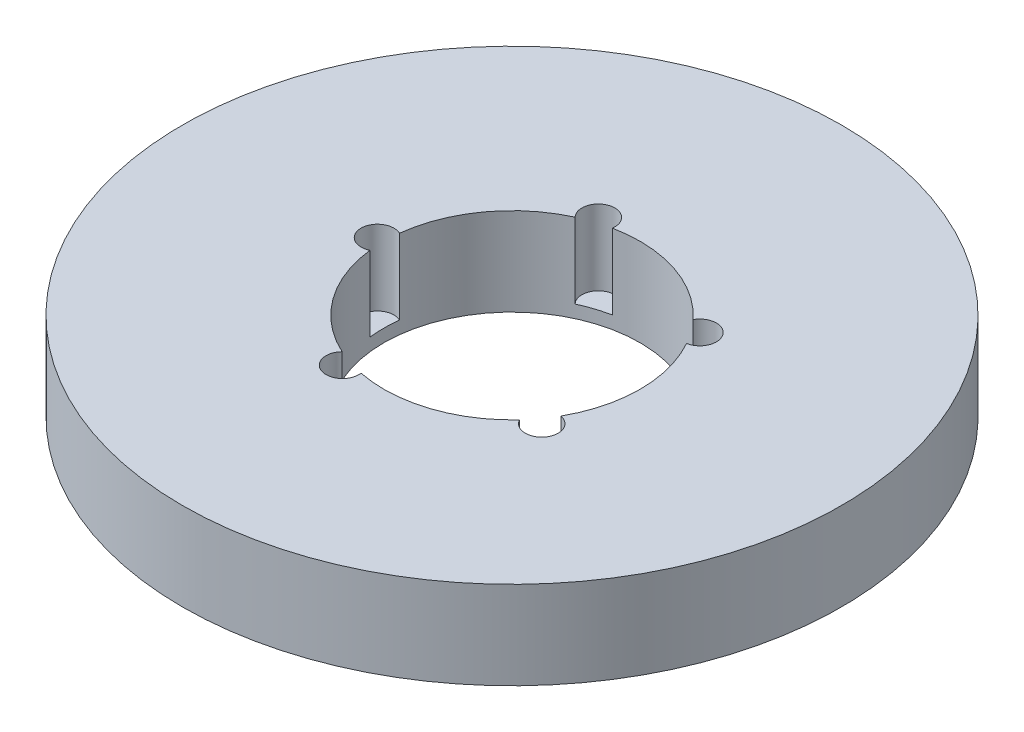
SolidWorks part; units mm, degrees
ref_plane "Front Plane" through (0, 0, 0) normal (0, 0, 1) x (1, 0, 0)
ref_plane "Top Plane" through (0, 0, 0) normal (0, 1, 0) x (1, 0, 0)
ref_plane "Right Plane" through (0, 0, 0) normal (1, 0, 0) x (0, 0, -1)
sketch "Sketch1" plane through (0, 0, 0) normal (0, 1, 0) x (1, 0, 0)
  circle A0 centre (0, 0) radius 90
  dimension "FLANGE_OD" = 180
extrude "Boss-Extrude1" add sketch "Sketch1" along normal blind 24
sketch "Sketch2" plane through (0, 0, 0) normal (0, 1, 0) x (1, 0, 0)
  circle A0 centre (0, 0) radius 35
  dimension "BORE_D" = 70
extrude "Cut-Extrude1" cut sketch "Sketch2" along normal through all
sketch "Sketch3" plane through (0, 24, 0) normal (0, 1, 0) x (1, 0, 0)
  circle A0 centre (0, 0) radius 36.7375 construction
  circle A1 centre (-36.7375, 0) radius 4.4905
  dimension "BOLT_D" = 8.9811
  dimension "BOLT_PCD" = 73.475
extrude "Cut-Extrude2" cut sketch "Sketch3" against normal blind 20.5378
pattern_circular "CirPattern1" count 5 over 360 about axis through (0, 0, 0) along (0, 1, 0) of "Cut-Extrude2"
